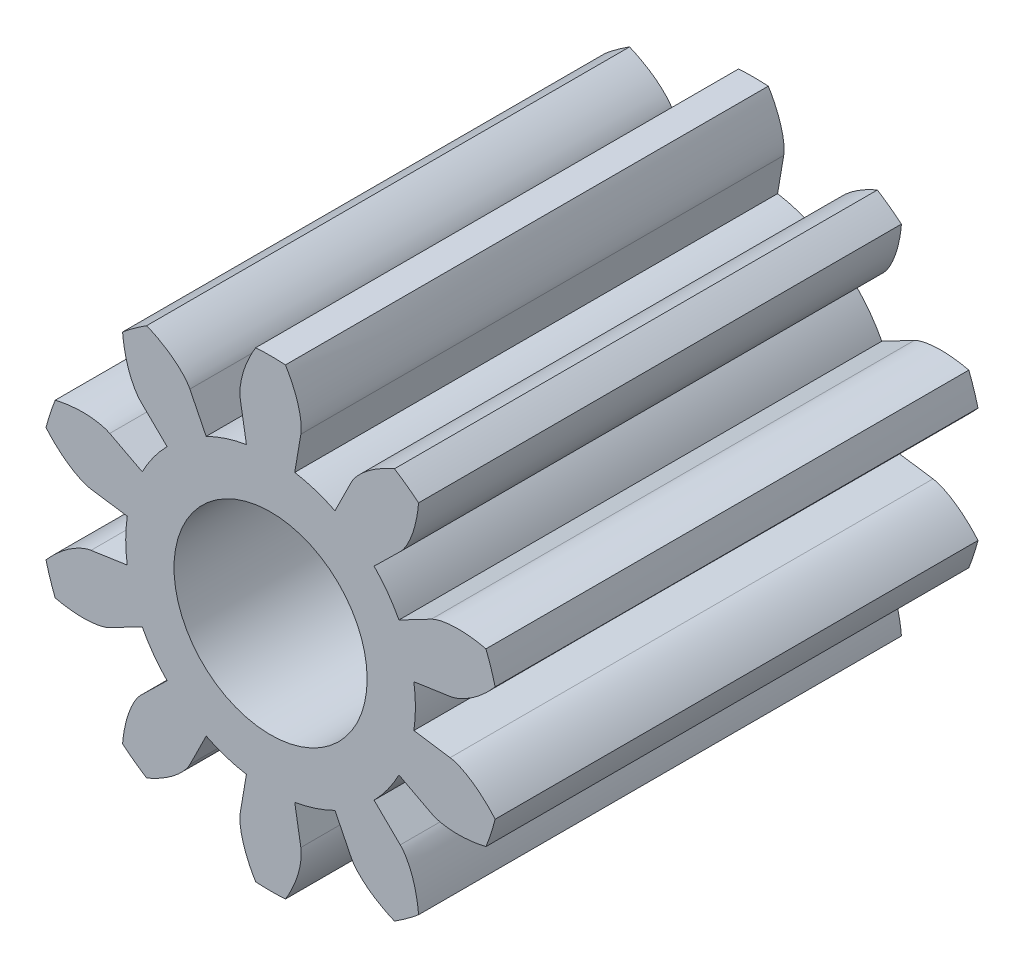
SolidWorks part; units mm, degrees
ref_plane "前视基准面" through (0, 0, 0) normal (0, 0, 1) x (1, 0, 0)
ref_plane "上视基准面" through (0, 0, 0) normal (0, 1, 0) x (1, 0, 0)
ref_plane "右视基准面" through (0, 0, 0) normal (1, 0, 0) x (0, 0, -1)
other "Configuration Table"
sketch "草图1" plane through (0, 0, 0) normal (0, 0, 1) x (1, 0, 0)
  line L0 (0, 0) -> (1, 0) construction
  line L1 (0, 0) -> (0.9877, 0.1564) construction
  line L2 (0, 0) -> (0.9296, 0.1372)
  line L3 (0.9877, 0.1564) -> (0.9877, -0.1564) construction
  line L4 (0, 0) -> (0.9296, -0.1372)
  circle A0 centre (0, 0) radius 1.2
  circle A1 centre (0, 0) radius 1 construction
  circle A2 centre (0, 0) radius 0.75
  circle A3 centre (0, 0) radius 0.9397 construction
  circle A4 centre (0, 0) radius 0.5
  spline S0 degree 4 poles (0.9296, 0.1372) (0.9367, 0.1383) (0.9563, 0.1427) (0.992, 0.1568) (1.0462, 0.1875) (1.1096, 0.2378) (1.181, 0.3131) (1.2504, 0.4131) (1.3102, 0.5327) (1.3562, 0.6693) (1.3849, 0.8103) (1.3976, 0.9537) (1.395, 1.1047) (1.3724, 1.2903) (1.3173, 1.5068) (1.2169, 1.7463) (1.0662, 1.9919) (0.881, 2.2132) (0.6689, 2.4075) (0.432, 2.5728) (0.1798, 2.7086) (-0.0913, 2.8136) (-0.364, 2.8888) (-0.6576, 2.9327) (-0.8809, 2.9465) (-1.1322, 2.9388) (-1.275, 2.9247) (-1.437, 2.9039) (-1.5236, 2.8844) (-1.5959, 2.871) (-1.6167, 2.8651) (-1.6321, 2.8616) knots 0 0 0 0 0 0.005604 0.015718 0.02996 0.048734 0.068727 0.096889 0.125051 0.153212 0.181374 0.209535 0.237696 0.271429 0.327752 0.384075 0.440398 0.496721 0.553044 0.609367 0.66569 0.722013 0.778336 0.834659 0.890982 0.909091 0.954545 0.977273 0.988636 1 1 1 1 1 construction
  spline S1 degree 4 poles (0.9296, 0.1372) (0.9367, 0.1383) (0.9563, 0.1427) (0.992, 0.1568) (1.0462, 0.1875) (1.1096, 0.2378) (1.181, 0.3131) (1.2504, 0.4131) (1.3102, 0.5327) (1.3562, 0.6693) (1.3849, 0.8103) (1.3976, 0.9537) (1.395, 1.1047) (1.3724, 1.2903) (1.3173, 1.5068) (1.2169, 1.7463) (1.0662, 1.9919) (0.881, 2.2132) (0.6689, 2.4075) (0.432, 2.5728) (0.1798, 2.7086) (-0.0913, 2.8136) (-0.364, 2.8888) (-0.6576, 2.9327) (-0.8809, 2.9465) (-1.0674, 2.9408) (-1.1539, 2.935) (-1.1748, 2.9334) knots 0 0 0 0 0 0.005604 0.015718 0.02996 0.048734 0.068727 0.096889 0.125051 0.153212 0.181374 0.209535 0.237696 0.271429 0.327752 0.384075 0.440398 0.496721 0.553044 0.609367 0.66569 0.722013 0.778336 0.834659 0.890982 0.909091 0.909091 0.909091 0.909091 0.909091
  spline S2 degree 4 poles (0.9296, -0.1372) (0.9367, -0.1383) (0.9563, -0.1427) (0.992, -0.1568) (1.0462, -0.1875) (1.1096, -0.2378) (1.181, -0.3131) (1.2504, -0.4131) (1.3102, -0.5327) (1.3562, -0.6693) (1.3849, -0.8103) (1.3976, -0.9537) (1.395, -1.1047) (1.3724, -1.2903) (1.3173, -1.5068) (1.2169, -1.7463) (1.0662, -1.9919) (0.881, -2.2132) (0.6689, -2.4075) (0.432, -2.5728) (0.1798, -2.7086) (-0.0913, -2.8136) (-0.364, -2.8888) (-0.6576, -2.9327) (-0.8809, -2.9465) (-1.1322, -2.9388) (-1.275, -2.9247) (-1.437, -2.9039) (-1.5236, -2.8844) (-1.5959, -2.871) (-1.6167, -2.8651) (-1.6321, -2.8616) knots 0 0 0 0 0 0.005604 0.015718 0.02996 0.048734 0.068727 0.096889 0.125051 0.153212 0.181374 0.209535 0.237696 0.271429 0.327752 0.384075 0.440398 0.496721 0.553044 0.609367 0.66569 0.722013 0.778336 0.834659 0.890982 0.909091 0.954545 0.977273 0.988636 1 1 1 1 1 construction
  spline S3 degree 4 poles (0.9296, -0.1372) (0.9367, -0.1383) (0.9563, -0.1427) (0.992, -0.1568) (1.0462, -0.1875) (1.1096, -0.2378) (1.181, -0.3131) (1.2504, -0.4131) (1.3102, -0.5327) (1.3562, -0.6693) (1.3849, -0.8103) (1.3976, -0.9537) (1.395, -1.1047) (1.3724, -1.2903) (1.3173, -1.5068) (1.2169, -1.7463) (1.0662, -1.9919) (0.881, -2.2132) (0.6689, -2.4075) (0.432, -2.5728) (0.1798, -2.7086) (-0.0913, -2.8136) (-0.364, -2.8888) (-0.6576, -2.9327) (-0.8809, -2.9465) (-1.0674, -2.9408) (-1.1539, -2.935) (-1.1748, -2.9334) knots 0 0 0 0 0 0.005604 0.015718 0.02996 0.048734 0.068727 0.096889 0.125051 0.153212 0.181374 0.209535 0.237696 0.271429 0.327752 0.384075 0.440398 0.496721 0.553044 0.609367 0.66569 0.722013 0.778336 0.834659 0.890982 0.909091 0.909091 0.909091 0.909091 0.909091
  point P15 (0.9877, 0)
  dimension "齿顶圆直径" = 2.4
  dimension "分度圆直径" = 2
  dimension "齿根圆直径" = 1.5
  dimension "基圆直径" = 1.8794
  dimension "内孔直径" = 1
  dimension "渐近线镜像线夹角" = 9
extrude "凸台-拉伸1" add sketch "草图1" along normal blind 2.5 contours A0 | A4
extrude "切除-拉伸1" cut sketch "草图1<3>" along normal through all contours A2 S3 A0 S1 region at (1.008, 0, 0)
sketch "草图1<3>" plane through (0, 0, 0) normal (0, 0, 1) x (1, 0, 0) same geometry as "草图1"
pattern_circular "阵列(圆周)1" count 10 every 36 about axis through (0, 0, 2.5) along (0, 0, 1) of "切除-拉伸1"
equation "\"m\"= 0.2'模数"
equation "\"z\" = 10'齿数"
equation "\"a\"= 20度'压力角"
equation "\"d\"= \"m\" * \"z\"'分度圆直径"
equation "\"da\"= ( \"z\" + 2 ) * \"m\"'齿顶圆直径"
equation "\"df\"= ( \"z\" - 2.5 ) * \"m\"'齿根圆直径"
equation "\"s\"= 0.5 * PI * \"m\"'分度圆齿厚"
equation "\"r\"= 0.38 * \"m\"'齿根圆角"
equation "\"B\"= 0.3 * \"d\"'齿厚"
equation "\"db\"= \"m\" * \"z\" * cos ( \"a\" )'基圆直径"
equation "\"rb\"= \"db\" / 2'基圆半径"
equation "\"齿顶圆直径@草图1\"= \"da\""
equation "\"分度圆直径@草图1\"= \"d\""
equation "\"齿根圆直径@草图1\"= \"df\""
equation "\"基圆直径@草图1\"= \"db\""
equation "\"渐近线镜像线夹角@草图1\"= 360 / 4 / \"z\""
equation "\"h\"= 2.5'齿轮厚度"
equation "\"ir\"= 1'内孔直径"
equation "\"内孔直径@草图1\"= \"ir\""
equation "\"齿轮厚@凸台-拉伸1\"= \"h\""
equation "\"齿轮夹角@阵列(圆周)1\"= 360 / \"z\""
equation "\"齿数@阵列(圆周)1\"= \"z\""
